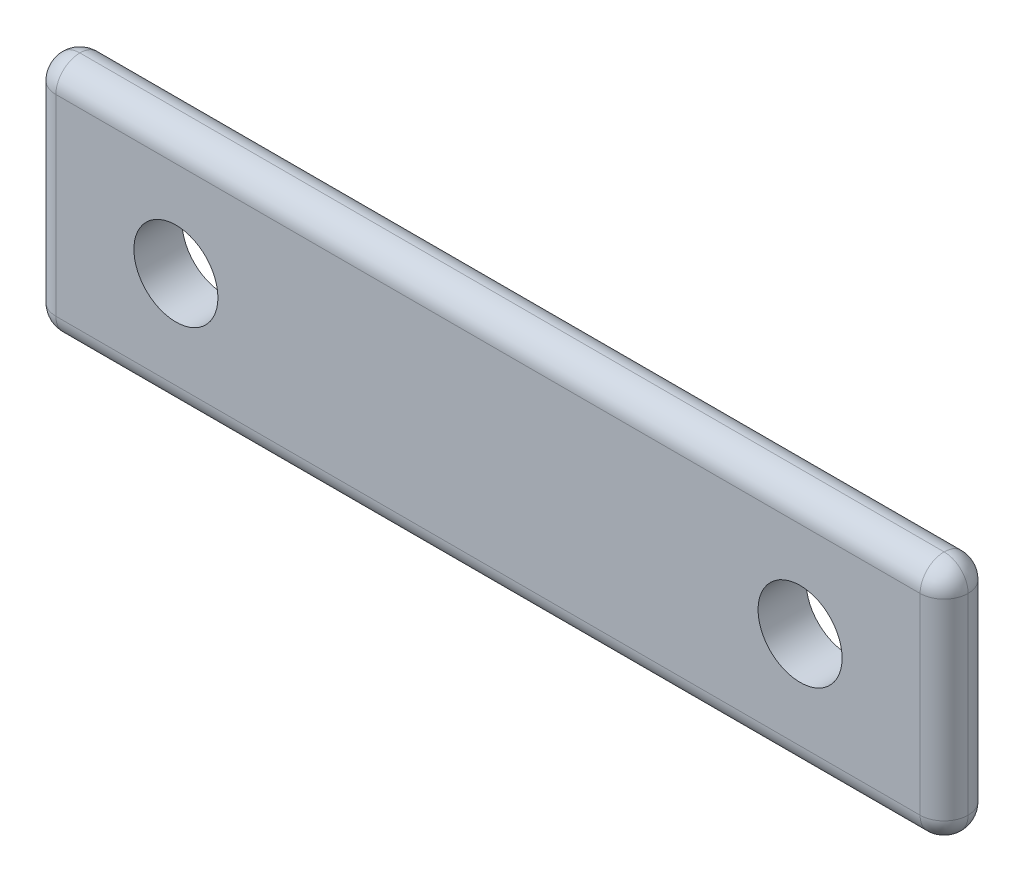
SolidWorks part; units mm, degrees
ref_plane "Plano frontal" through (0, 0, 0) normal (0, 0, 1) x (1, 0, 0)
ref_plane "Plano superior" through (0, 0, 0) normal (0, 1, 0) x (1, 0, 0)
ref_plane "Plano direito" through (0, 0, 0) normal (1, 0, 0) x (0, 0, -1)
sketch "Esboço1" plane through (0, 0, 0) normal (0, 0, 1) x (1, 0, 0)
  line L4 (0, 0) -> (0, 50)
  line L5 (0, 50) -> (190, 50)
  line L6 (190, 50) -> (190, 0)
  line L7 (190, 0) -> (0, 0)
  dimension "D1" = 190
  dimension "D2" = 50
extrude "Ressalto-extrusão1" add sketch "Esboço1" along normal blind 10
fillet "Filete1" radius 5 8 edges at (190, 25, 0) (190, 25, 10) (0, 25, 0) (0, 25, 10) (95, 0, 0) (95, 0, 10) (95, 50, 0) (95, 50, 10)
hole_wizard "Broca de rosquear para tarraxa de M201" positions "Esboço7" profile "Esboço8" hole size "M20" standard "DIN" end condition through all
sketch "Esboço7" plane through (0, 0, 10) normal (0, 0, 1) x (1, 0, 0)
  line L0 (0, 5) -> (0, 45) construction
  line L1 (190, 45) -> (190, 5) construction
  point P0 (30, 25.2069)
  point P2 (160, 25.2069)
  dimension "D1" = 30
  dimension "D2" = 30
sketch "Esboço8" plane through (30, 25.2069, 10) normal (1, 0, 0) x (0, -1, 0)
  line L0 (0, 0) -> (0, 10)
  line L1 (0, 10) -> (8.75, 10)
  line L2 (8.75, 10) -> (8.75, 0)
  line L5 (8.75, 0) -> (0, 0)
  line L11 (0, -6.35) -> (0, 107.95) construction
  dimension "Thru Hole Dia." = 17.5
  dimension "Thru Hole Depth" = 10
